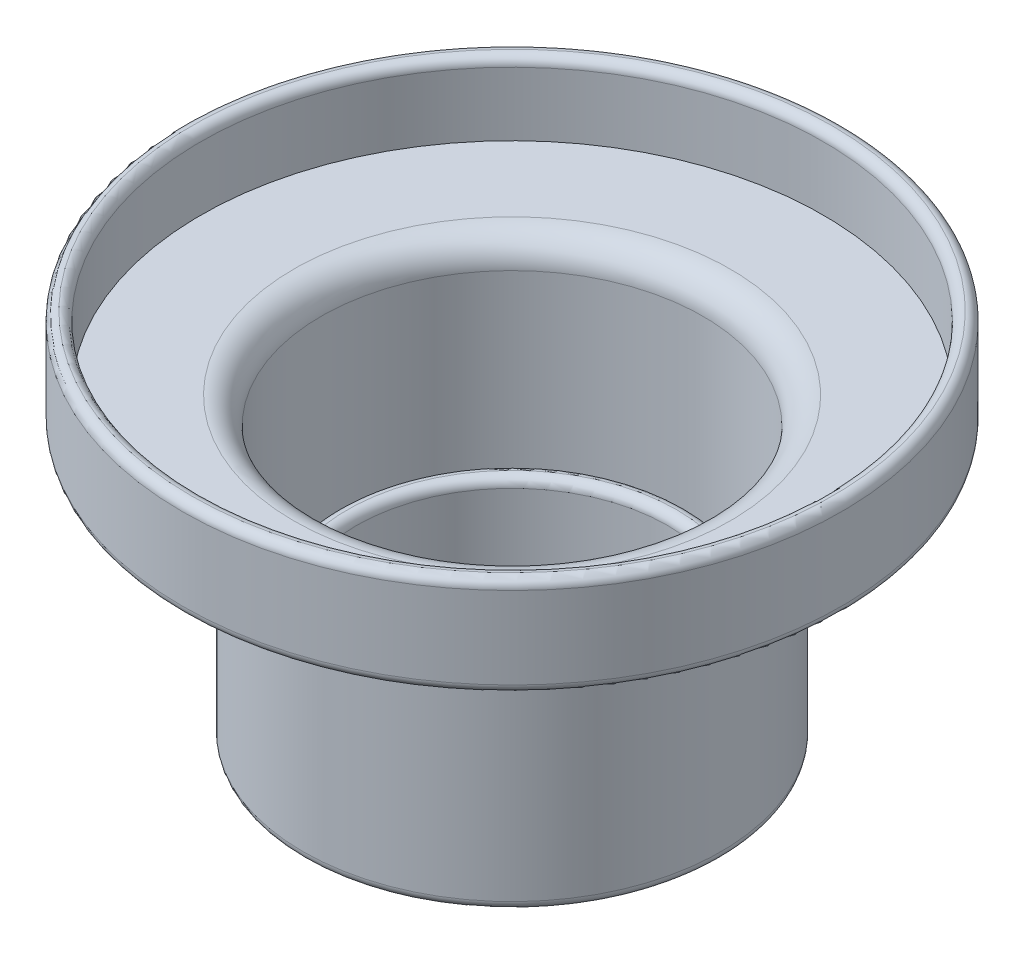
SolidWorks part; units mm, degrees
ref_plane "Front Plane" through (0, 0, 0) normal (0, 0, 1) x (1, 0, 0)
ref_plane "Top Plane" through (0, 0, 0) normal (0, 1, 0) x (1, 0, 0)
ref_plane "Right Plane" through (0, 0, 0) normal (1, 0, 0) x (0, 0, -1)
ref_plane "Plane1" through (0, 10, 0) normal (0, 1, 0) x (1, 0, 0)
ref_plane "Plane2" through (0, 30, 0) normal (0, 1, 0) x (1, 0, 0)
sketch "Sketch1" plane through (0, 0, 0) normal (0, 1, 0) x (1, 0, 0)
  circle A0 centre (0, 0) radius 19.125
  circle A1 centre (0, 0) radius 17.125
  dimension "D1" = 38.25
  dimension "D2" = 2
extrude "Boss-Extrude1" add sketch "Sketch1" along normal up to surface (10 mm away) up to plane "Plane1"
sketch "Sketch2" plane through (0, 0, 0) normal (0, 1, 0) x (1, 0, 0)
  circle A0 centre (0, 0) radius 21
  circle A1 centre (0, 0) radius 23
  dimension "D1" = 42
  dimension "D2" = 2
extrude "Boss-Extrude2" add sketch "Sketch2" along normal up to surface (30 mm away) separate body up to plane "Plane2"
sketch "Sketch3" plane through (0, 0, 0) normal (0, 1, 0) x (1, 0, 0)
  circle A0 centre (0, 0) radius 23 construction
  circle A1 centre (0, 0) radius 23
  circle A2 centre (0, 0) radius 17.125 construction
  circle A3 centre (0, 0) radius 17.125
extrude "Boss-Extrude3" add sketch "Sketch3" against normal blind 3
sketch "Sketch4" plane through (0, 30, 0) normal (0, 1, 0) x (1, 0, 0)
  circle A0 centre (0, 0) radius 21 construction
  circle A1 centre (0, 0) radius 21
  circle A2 centre (0, 0) radius 36.25
  dimension "D1" = 72.5
extrude "Boss-Extrude4" add sketch "Sketch4" against normal blind 3
sketch "Sketch5" plane through (0, 30, 0) normal (0, 1, 0) x (1, 0, 0)
  circle A0 centre (0, 0) radius 34.25
  circle A1 centre (0, 0) radius 36.25
  circle A2 centre (0, 0) radius 36.25
  circle A3 centre (0, 0) radius 21
  circle A4 centre (0, 0) radius 21
  dimension "D1" = 0
  dimension "D2" = 0
  dimension "D3" = 2
extrude "Boss-Extrude5" add sketch "Sketch5" along normal blind 8 contours A2 A0 region at (-35.2247, 30, 0)
fillet "Fillet1" radius 5 1 edges at (0, 27, 23)
fillet "Fillet2" radius 3 1 edges at (0, 30, 21)
fillet "Fillet3" radius 1 7 edges at (0, 38, 36.25) (0, 38, 34.25) (0, -3, 23) (0, 27, 36.25) (0, 10, 17.125) (0, 10, 19.125) (0, -3, 17.125)
